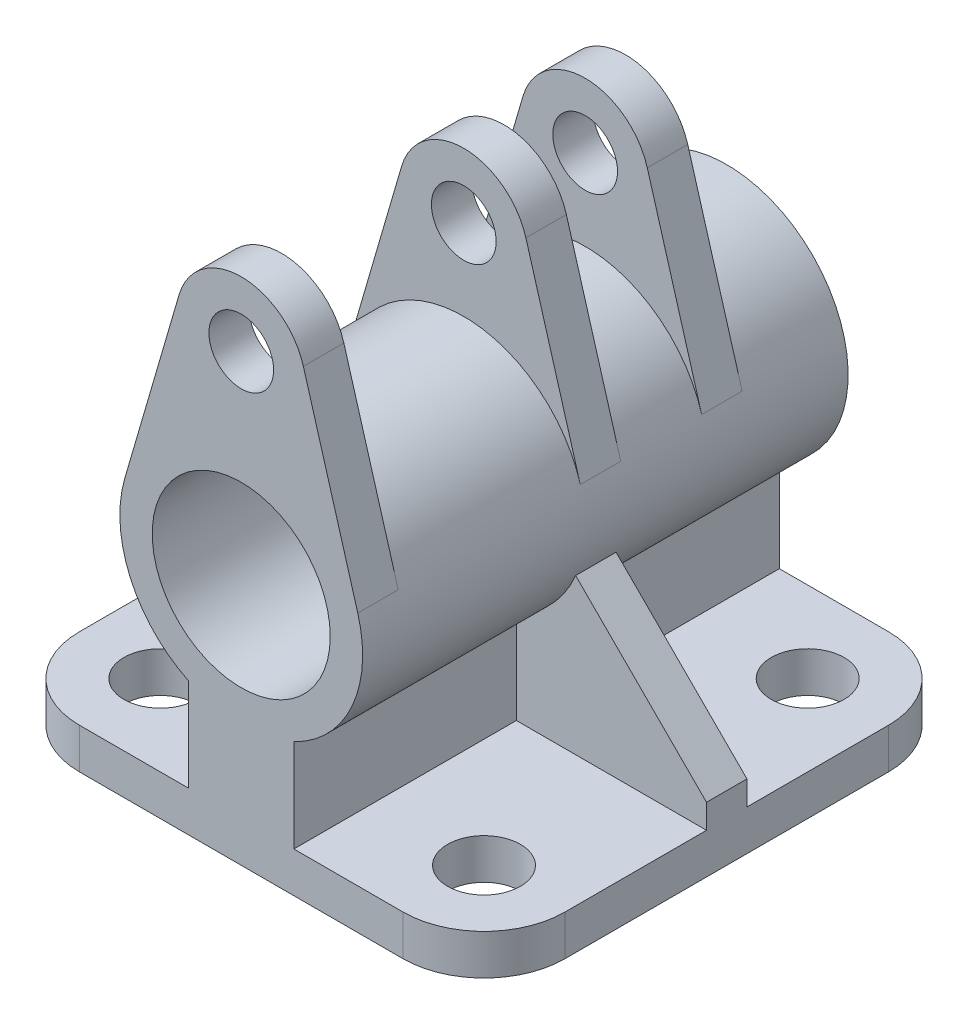
SolidWorks part; units mm, degrees
ref_plane "Спереди" through (0, 0, 0) normal (0, 0, 1) x (1, 0, 0)
ref_plane "Сверху" through (0, 0, 0) normal (0, 1, 0) x (1, 0, 0)
ref_plane "Справа" through (0, 0, 0) normal (1, 0, 0) x (0, 0, -1)
sketch "Эскиз1" plane through (0, 0, 0) normal (0, 0, 1) x (1, 0, 0)
  line L0 (0, -15) -> (0, -64.812) construction
  line L1 (6.5, -13.5185) -> (6.5, -25)
  line L2 (-30, -30) -> (30, -30)
  line L3 (13.8234, -5.8234) -> (30, -22)
  line L4 (30, -30) -> (30, -22)
  line L5 (30, -25) -> (6.5, -25)
  line L6 (0, -15) -> (0, 33) construction
  line L7 (-14.4, 4.2) -> (-7.68, 27.24)
  line L8 (7.68, 27.24) -> (14.4, 4.2)
  line L9 (-13.8234, -5.8234) -> (-30, -22)
  line L10 (-6.5, -13.5185) -> (-6.5, -25)
  line L11 (-30, -25) -> (-6.5, -25)
  line L12 (-30, -30) -> (-30, -22)
  circle A0 centre (0, 0) radius 11
  circle A1 centre (0, 0) radius 15
  arc A2 (7.68, 27.24) -> (-7.68, 27.24) centre (0, 25) ccw
  circle A3 centre (0, 25) radius 4
  point P26 (0, -30)
  dimension "D1" = 22
  dimension "D2" = 30
  dimension "D9" = 8
  dimension "D10" = 55
  dimension "D11" = 63
  dimension "D3" = 13
  dimension "D4" = 30
  dimension "D5" = 8
  dimension "D6" = 5
  dimension "D7" = 45
  dimension "D8" = 60
extrude "Бобышка-Вытянуть3" add sketch "Эскиз1" along normal mid plane 60 contours A1 A0 | A1 L10 L11 L12 L2 L4 L5 L1 region at (0, -25.0787, 0) region at (0, -14.5757, 0)
extrude "Бобышка-Вытянуть4" add sketch "Эскиз1<6>" along normal mid plane 5 contours L8 A2 L7 A1 A3 | A1 L1 L5 L4 L3 | A1 L9 L12 L11 L10 region at (16.4394, -18.1684, 0) region at (-16.4394, -18.1684, 0) region at (0, 20.665, 0)
sketch "Эскиз1<6>" plane through (0, 0, 0) normal (0, 0, 1) x (1, 0, 0) same geometry as "Эскиз1"
extrude "Бобышка-Вытянуть5" add sketch "Эскиз1<9>" along normal mid plane 5 from offset 15 contours L8 A2 L7 A1 A3 region at (0, 20.665, 0) offset against normal yes
sketch "Эскиз1<9>" plane through (0, 0, 0) normal (0, 0, 1) x (1, 0, 0) same geometry as "Эскиз1"
extrude "Бобышка-Вытянуть7" add sketch "Эскиз1<12>" against normal blind 5 from vertex contours L8 A2 L7 A1 A3 region at (0, 20.665, 0) starting at point (-30, -25, 30)
sketch "Эскиз1<12>" plane through (0, 0, 0) normal (0, 0, 1) x (1, 0, 0) same geometry as "Эскиз1"
sketch "Эскиз3" plane through (0, -30, 0) normal (0, -1, 0) x (1, 0, 0)
  line L0 (0, 30) -> (0, -30) construction
  line L1 (-30, 30) -> (30, 30) construction
  line L2 (-30, -30) -> (30, -30) construction
  line L3 (-30, 0) -> (30, 0) construction
  line L4 (-30, 30) -> (-30, -30) construction
  line L5 (30, 30) -> (30, -30) construction
  circle A0 centre (20, -20) radius 4.5
  dimension "D2" = 9
  dimension "D1" = 20
  dimension "D3" = 20
extrude "Вырез-Вытянуть3" cut sketch "Эскиз3" against normal through all contours A0
mirror "Зеркальное отражение1" about plane through (0, 0, 0) normal (1, 0, 0) of "Вырез-Вытянуть3"
mirror "Зеркальное отражение2" about plane through (0, 0, 0) normal (0, 0, 1) of "Вырез-Вытянуть3", "Зеркальное отражение1"
fillet "Скругление1" radius 10 4 edges at (30, -27.5, 30) (30, -27.5, -30) (-30, -27.5, -30) (-30, -27.5, 30)
